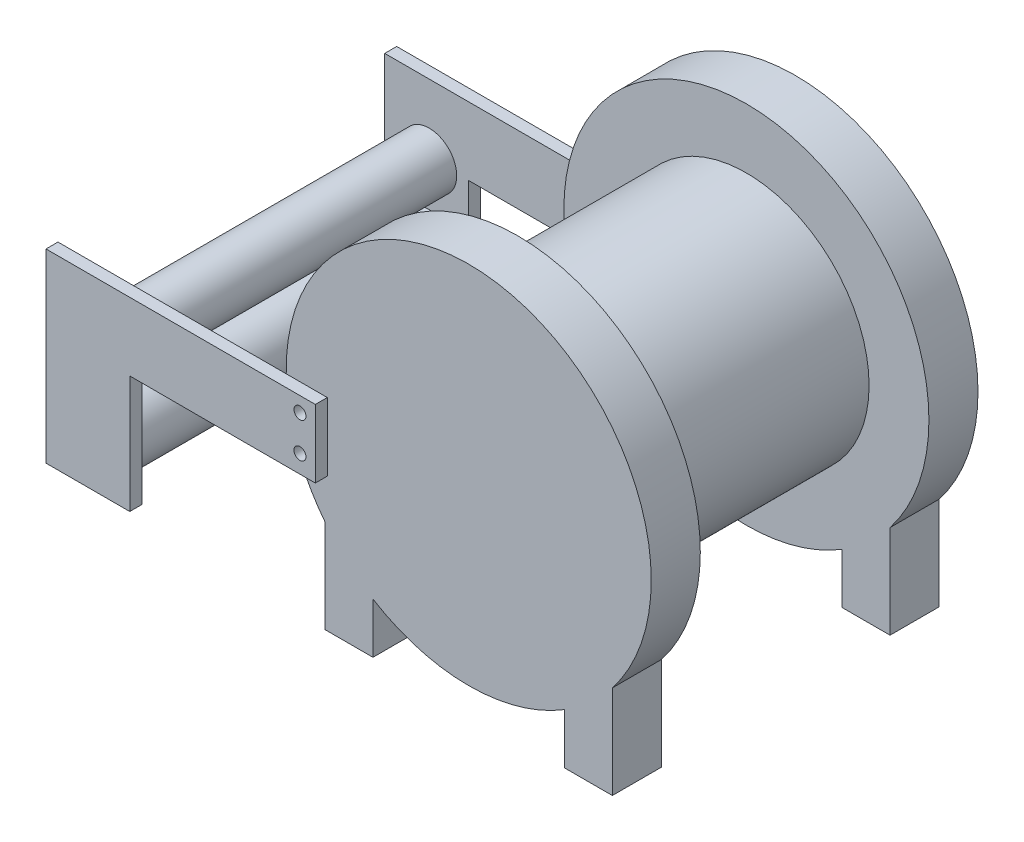
SolidWorks part; units mm, degrees
ref_plane "Front Plane" through (0, 0, 0) normal (0, 0, 1) x (1, 0, 0)
ref_plane "Top Plane" through (0, 0, 0) normal (0, 1, 0) x (1, 0, 0)
ref_plane "Right Plane" through (0, 0, 0) normal (1, 0, 0) x (0, 0, -1)
sketch "Sketch1" plane through (0, 0, 0) normal (0, 0, 1) x (1, 0, 0)
  line L0 (-152.5, 0) -> (152.5, 0) construction
  line L1 (-152.5, 345) -> (152.5, 345) construction
  line L2 (0, 345) -> (0, 0) construction
  line L3 (-152.5, 345) -> (-152.5, 0) construction
  line L4 (152.5, 345) -> (152.5, 0) construction
  line L5 (-152.5, 172) -> (152.5, 172) construction
  line L6 (-100, 345) -> (-100, 0) construction
  line L7 (-120, 172) -> (-120, 0) construction
  line L8 (-80, 172) -> (-80, 0) construction
  line L9 (-120, 77.8923) -> (-120, 0)
  line L10 (-80, 42.1684) -> (-80, 0)
  line L11 (-120, 0) -> (-80, 0)
  line L12 (80, 42.1684) -> (80, 0)
  line L13 (120, 0) -> (80, 0)
  line L14 (120, 77.8923) -> (120, 0)
  arc A0 (-80, 42.1684) -> (80, 42.1684) centre (0, 172) ccw
  arc A1 (120, 77.8923) -> (-120, 77.8923) centre (0, 172) ccw
  circle A2 centre (0, 172) radius 102.5
  point P5 (0, 0)
  point P7 (0, 172)
  dimension "D6" = 205
  dimension "D1" = 345
  dimension "D2" = 152.5
  dimension "D3" = 172
  dimension "D4" = 20
  dimension "D5" = 100
extrude "Boss-Extrude1" add sketch "Sketch1" along normal blind 41 contours L14 A1 L9 L11 L10 A0 L12 L13 A2 | A2 region at (0, 320.0466, 0) region at (0, 172, 0)
extrude "Boss-Extrude2" add sketch "Sketch1<3>" along normal blind 191 from surface contours A2 region at (0, 172, 0) starting at face at (0, 58.0076, 41)
sketch "Sketch1<3>" plane through (0, 0, 0) normal (0, 0, 1) x (1, 0, 0) same geometry as "Sketch1"
extrude "Boss-Extrude3" add sketch "Sketch1<4>" along normal blind 41 from surface contours L14 A1 L9 L11 L10 A0 L12 L13 A2 | A2 region at (0, 320.0466, 0) region at (0, 172, 0) starting at face at (102.5, 172, 232)
sketch "Sketch1<4>" plane through (0, 0, 0) normal (0, 0, 1) x (1, 0, 0) same geometry as "Sketch1"
sketch "Sketch2" plane through (0, 0, 0) normal (0, 0, -1) x (-1, 0, 0)
  line L0 (131, 0) -> (131, 250.0721) construction
  line L1 (0, 172) -> (200.3709, 172) construction
  line L2 (118.1728, 140.45) -> (140.0895, 140.45) construction
  line L3 (118.1728, 168.9) -> (118.1728, 112)
  line L4 (118.1728, 168.9) -> (143.8272, 168.9)
  line L5 (143.8272, 168.9) -> (143.8272, 112)
  line L6 (120, 0) -> (120, 77.8923)
  line L7 (80, 0) -> (120, 0)
  line L8 (80, 42.1684) -> (80, 0)
  line L9 (-80, 0) -> (-80, 42.1684)
  line L10 (-120, 0) -> (-80, 0)
  line L11 (-120, 77.8923) -> (-120, 0)
  line L12 (120, 0) -> (120, 77.8923)
  line L13 (80, 0) -> (120, 0)
  line L14 (80, 42.1684) -> (80, 0)
  line L15 (-80, 0) -> (-80, 42.1684)
  line L16 (-120, 0) -> (-80, 0)
  line L17 (-120, 77.8923) -> (-120, 0)
  line L18 (118.1728, 112) -> (143.8272, 112)
  line L19 (61.7663, 18.0693) -> (144.394, 18.0693) construction
  circle A0 centre (131, 156.4) radius 5
  circle A1 centre (0, 172) radius 102.5
  circle A2 centre (0, 172) radius 102.5
  arc A4 (-80, 42.1684) -> (80, 42.1684) centre (0, 172) ccw
  arc A5 (120, 77.8923) -> (-120, 77.8923) centre (0, 172) ccw
  arc A6 (-80, 42.1684) -> (80, 42.1684) centre (0, 172) ccw
  arc A7 (120, 77.8923) -> (-120, 77.8923) centre (0, 172) ccw
  circle A9 centre (131, 127) radius 5
  point P26 (131, 168.9)
  point P30 (143.8272, 140.45)
  dimension "D6" = 15
  dimension "D9" = 10
  dimension "D3" = 112
  dimension "D4" = 56.9
  dimension "D5" = 12.5
  dimension "D7" = 11
  dimension "D8" = 25.6544
  dimension "D1" = 0
  dimension "D2" = 0
sketch "Sketch3" plane through (0, 0, 0) normal (0, 0, 1) x (1, 0, 0)
  line L0 (-131, 140.45) -> (-306, 140.45) construction
  line L1 (-118.1728, 140.45) -> (-140.0895, 140.45) construction
  line L2 (-131, 0) -> (-131, 250.0721) construction
  line L3 (-131, 112) -> (-306, 112) construction
  line L4 (-118.1728, 112) -> (-143.8272, 112) construction
  line L9 (-118.1728, 112) -> (-118.1728, 168.9)
  line L10 (-118.1728, 168.9) -> (-273.1728, 168.9)
  line L14 (-306, 168.9) -> (-306, 46.9) construction
  line L15 (-131, 168.9) -> (-306, 168.9) construction
  line L16 (-343.1728, 13.9) -> (-273.1728, 13.9)
  line L17 (-273.1728, 112) -> (-273.1728, 13.9)
  line L18 (-118.1728, 112) -> (-273.1728, 112)
  line L19 (-343.1728, 168.9) -> (-118.1728, 168.9)
  line L20 (-343.1728, 13.9) -> (-343.1728, 168.9)
  circle A0 centre (-131, 156.4) radius 5
  circle A1 centre (-131, 127) radius 5
  circle A4 centre (-306, 110.4) radius 23
  circle A5 centre (-306, 46.9) radius 27.5
  point P10 (0, 0)
  point P17 (-281.4702, 105.4708)
  point P20 (-273.1728, 169.1167)
  point P29 (-314.9793, 267)
  point P31 (-342.2477, 267)
  dimension "D3" = 55
  dimension "D4" = 46
  dimension "D5" = 122
  dimension "D9" = 10
  dimension "D2" = 114
  dimension "D1" = 175
  dimension "D6" = 70
  dimension "D7" = 225
  dimension "D8" = 155
extrude "Boss-Extrude4" add sketch "Sketch3" against normal blind 10 contours L20 L16 L17 L18 L9 L10 L19 A4 A1 A0 A5 | A5 | A4 region at (-246.421, 123.6361, 0) region at (-306, 110.4, 0) region at (-306, 46.9, 0)
ref_plane "Plane1" through (0, 0, 136.5) normal (0, 0, -1) x (-1, 0, 0)
mirror "Mirror1" about plane through (0, 0, 136.5) normal (0, 0, -1) of "Boss-Extrude4"
extrude "Boss-Extrude5" add sketch "Sketch3<3>" along normal up to surface (273 mm away) from surface contours A4 | A5 region at (-306, 110.4, 0) region at (-306, 46.9, 0) up to face at (-254.6834, 98.1682, 273) starting at face at (-254.6834, 98.1682, 0)
sketch "Sketch3<3>" plane through (0, 0, 0) normal (0, 0, 1) x (1, 0, 0) same geometry as "Sketch3"
sketch "Sketch4" plane through (0, 0, 136.5) normal (0, 0, -1) x (-1, 0, 0)
  circle A0 centre (0, 172) radius 102.5 construction
  circle A1 centre (0, 172) radius 102.5
